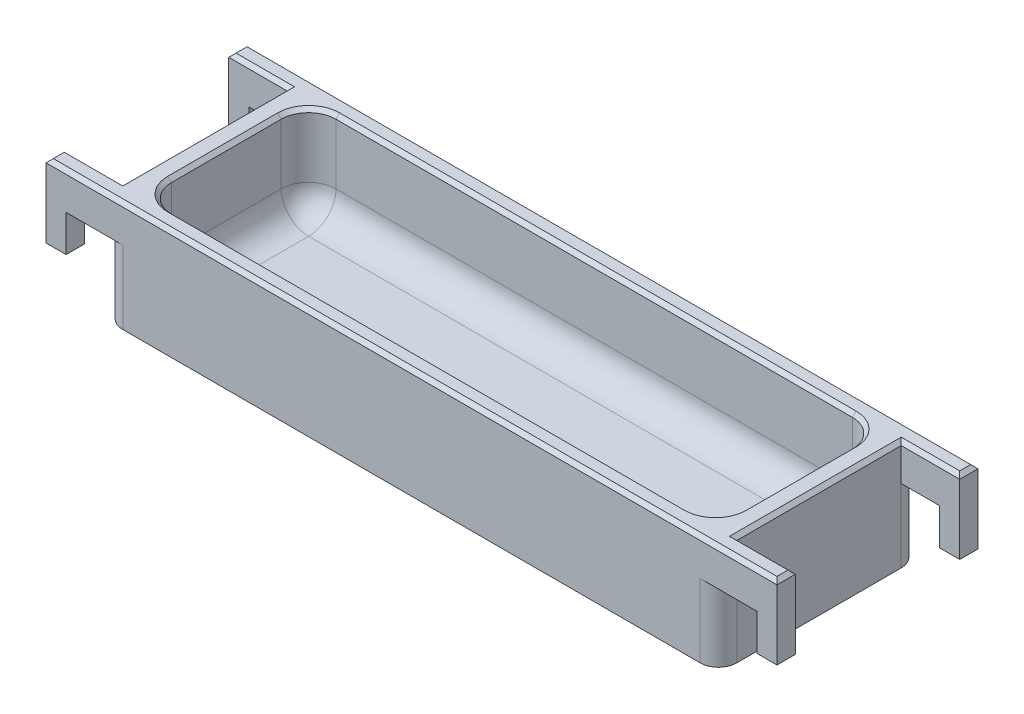
SolidWorks part; units mm, degrees
ref_plane "Front Plane" through (0, 0, 0) normal (0, 0, 1) x (1, 0, 0)
ref_plane "Top Plane" through (0, 0, 0) normal (0, 1, 0) x (1, 0, 0)
ref_plane "Right Plane" through (0, 0, 0) normal (1, 0, 0) x (0, 0, -1)
sketch "Sketch1" plane through (0, 0, 0) normal (0, 1, 0) x (1, 0, 0)
  line L0 (-84, -15) -> (-84, -20)
  line L1 (-100, 30) -> (100, 30)
  line L2 (-100, 30) -> (-100, 25)
  line L3 (-100, -20) -> (-84, -20)
  line L4 (100, 30) -> (100, 25)
  line L5 (-78.1495, -20) -> (78.1495, -20)
  line L6 (-100, -20) -> (-84, -20)
  line L8 (-84, 25) -> (-84, -15)
  line L10 (84, 25) -> (84, -15)
  line L13 (-84, 25) -> (-100, 25)
  line L14 (-84, 25) -> (-84, -15)
  line L18 (84, -15) -> (84, 25)
  line L19 (84, 25) -> (100, 25)
  line L21 (-100, -20) -> (-84, -20)
  line L24 (-78.1495, -15) -> (-78.1495, 25)
  line L25 (-78.1495, 25) -> (78.1495, 25)
  line L26 (78.1495, -15) -> (78.1495, 25)
  line L27 (84, -20) -> (100, -20)
  line L28 (84, -20) -> (100, -20)
  line L29 (-78.1495, 25) -> (78.1495, 25)
  line L30 (-100, -20) -> (-100, -25)
  line L31 (-100, -25) -> (100, -25)
  line L32 (100, -20) -> (100, -25)
  line L33 (-78.1495, -15) -> (-78.1495, -20)
  line L34 (78.1495, -15) -> (78.1495, -20)
  line L36 (84, -20) -> (84, -15)
  line L37 (-78.1495, -20) -> (78.1495, -20)
  point P0 (0, 0)
  point P6 (0, 0)
  point P15 (0, 0)
  dimension "D1" = 200
  dimension "D2" = 50
  dimension "D3" = 5
  dimension "D4" = 168
extrude "Boss-Extrude1" add sketch "Sketch1" along normal blind 30 contours L10 L19 L4 L1 L2 L13 L8 L3 L26 L24 L25 region at (-81.9258, 0, -5)
sketch "Sketch3" plane through (0, 0, -25) normal (0, 0, 1) x (1, 0, 0)
  line L1 (-84, 0) -> (-94.5, 0)
  line L2 (-84, 0) -> (-84, 20)
  line L3 (-84, 20) -> (-94.5, 20)
  line L4 (-94.5, 11.6805) -> (-94.5, 20)
  line L7 (-100, 0) -> (-94.5, 0)
  line L9 (-100, 30) -> (-100, 0) construction
  line L10 (-100, 10) -> (-94.5, 10)
  line L11 (-94.5, 10) -> (-94.5, 11.6805)
  line L12 (-100, 10) -> (-100, 0)
  dimension "D1" = 10.5
  dimension "D2" = 20
extrude "Cut-Extrude1" cut sketch "Sketch3" against normal blind 5
ref_plane "Plane1" through (0, 0, -2.5) normal (0, 0, 1) x (1, 0, 0)
mirror "Mirror1" about plane through (0, 0, -2.5) normal (0, 0, 1) of "Cut-Extrude1" second plane through (0, 0, 0) second plane normal (1, 0, 0)
sketch "Sketch4" plane through (0, 0, 0) normal (0, -1, 0) x (1, 0, 0)
  line L10 (-78.1495, 20) -> (78.1495, 20)
  line L11 (-78.1495, 20) -> (-78.1495, -25)
  line L12 (-78.1495, -25) -> (78.1495, -25)
  line L13 (78.1495, 20) -> (78.1495, -25)
extrude "Boss-Extrude2" add sketch "Sketch4" against normal blind 5
fillet "Fillet1" radius 7.5 8 edges at (0, 5, -25) (78.1495, 5, -2.5) (-78.1495, 5, -2.5) (78.1495, 17.5, -25) (-78.1495, 17.5, -25) (0, 5, 20) (-78.1495, 17.5, 20) (78.1495, 17.5, 20)
fillet "Fillet2" radius 5 4 edges at (84, 10, -30) (-84, 10, -30) (84, 10, 25) (-84, 10, 25)
chamfer "Chamfer1" distance 1 angle 45 20 edges at (100, 30, 22.5) (0, 30, 25) (-100, 30, 22.5) (-92, 30, 20) (-84, 30, -2.5) (-92, 30, -25) (-100, 30, -27.5) (0, 30, -30) (100, 30, -27.5) (92, 30, -25) (84, 30, -2.5) (92, 30, 20) (75.9528, 30, -22.8033) (0, 30, -25) (-75.9528, 30, -22.8033) (-78.1495, 30, -2.5) (-75.9528, 30, 17.8033) (0, 30, 20) (75.9528, 30, 17.8033) (78.1495, 30, -2.5)
